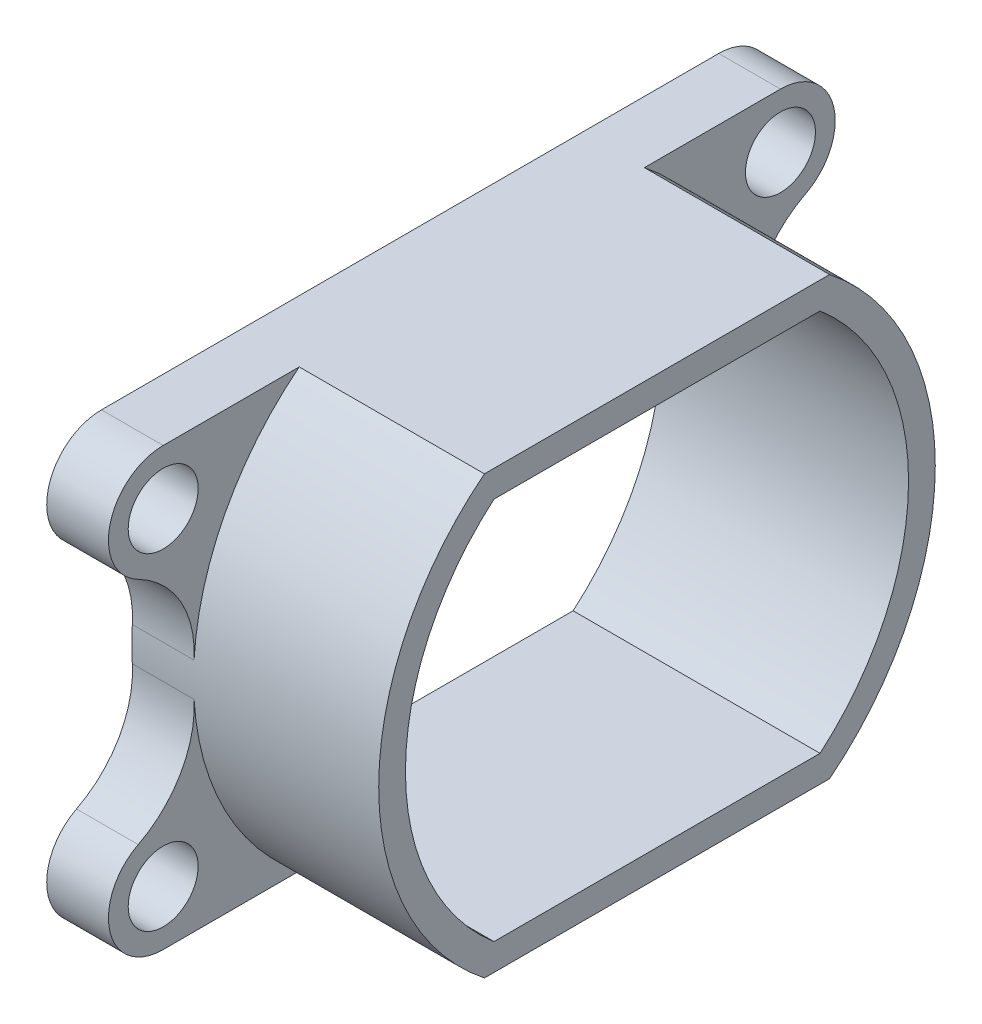
SolidWorks part; units mm, degrees
ref_plane "Front Plane" through (0, 0, 0) normal (0, 0, 1) x (1, 0, 0)
ref_plane "Top Plane" through (0, 0, 0) normal (0, 1, 0) x (1, 0, 0)
ref_plane "Right Plane" through (0, 0, 0) normal (1, 0, 0) x (0, 0, -1)
sketch "Sketch1" plane through (0, 0, 0) normal (1, 0, 0) x (0, 0, -1)
  line L0 (-7.8677, -9.16) -> (7.8677, -9.16) construction
  line L1 (-7.8677, 9.16) -> (7.8677, 9.16) construction
  line L2 (-7.8677, -9.16) -> (7.8677, 9.16) construction
  line L3 (-7.8677, 9.16) -> (7.8677, -9.16) construction
  line L4 (-7.923, 9.31) -> (7.923, 9.31)
  line L5 (-7.923, -9.31) -> (7.923, -9.31)
  line L6 (-8.3877, 10.61) -> (8.3877, 10.61)
  line L7 (-8.3877, -10.61) -> (8.3877, -10.61)
  arc A0 (-7.8677, 9.16) -> (-7.8677, -9.16) centre (0, 0) ccw construction
  arc A1 (7.8677, -9.16) -> (7.8677, 9.16) centre (0, 0) ccw construction
  arc A2 (7.923, -9.31) -> (7.923, 9.31) centre (0, 0) ccw
  arc A3 (-7.923, 9.31) -> (-7.923, -9.31) centre (0, 0) ccw
  arc A4 (8.3877, -10.61) -> (8.3877, 10.61) centre (0, 0) ccw
  arc A5 (-8.3877, 10.61) -> (-8.3877, -10.61) centre (0, 0) ccw
  point P0 (0, 0)
  point P6 (0, 0)
  point P20 (8.6275, -11.31)
  dimension "D2" = 24.15
  dimension "D1" = 18.32
  dimension "D3" = 0.15
  dimension "D4" = 1.3
extrude "Motor Holder" add sketch "Sketch1" along normal blind 12
sketch "Sketch2" plane through (0, 0, 0) normal (-1, 0, 0) x (0, 0, 1)
  line L4 (0, 0) -> (0, 27.8421) construction
  line L5 (0, 0) -> (-9.5877, 0) construction
  line L7 (8.3877, 10.61) -> (15, 10.61)
  line L24 (15.862, 5.4335) -> (12.7951, 4.383)
  line L25 (15.862, -5.4335) -> (12.7951, -4.383)
  line L26 (8.3877, -10.61) -> (15, -10.61)
  line L27 (-8.3877, -10.61) -> (-15, -10.61)
  line L28 (-15.862, -5.4335) -> (-12.7951, -4.383)
  line L29 (-15.862, 5.4335) -> (-12.7951, 4.383)
  line L30 (-8.3877, 10.61) -> (-15, 10.61)
  circle A10 centre (15, 7.95) radius 1.7
  circle A12 centre (-15, 7.95) radius 1.7
  circle A13 centre (15, -7.95) radius 1.7
  circle A14 centre (-15, -7.95) radius 1.7
  arc A16 (-8.3877, 10.61) -> (-8.3877, -10.61) centre (0, 0) ccw construction
  arc A20 (15, 10.61) -> (15.862, 5.4335) centre (15, 7.95) cw
  arc A21 (8.3877, 10.61) -> (12.7951, 4.383) centre (0, 0) cw
  arc A22 (-8.3877, 10.61) -> (-8.3877, -10.61) centre (0, 0) ccw
  arc A31 (-8.3877, 10.61) -> (-8.3877, -10.61) centre (0, 0) ccw
  arc A32 (8.3877, -10.61) -> (8.3877, 10.61) centre (0, 0) ccw construction
  arc A33 (15, -10.61) -> (15.862, -5.4335) centre (15, -7.95) ccw
  arc A34 (8.3877, -10.61) -> (12.7951, -4.383) centre (0, 0) ccw
  arc A35 (-8.3877, -10.61) -> (-12.7951, -4.383) centre (0, 0) cw
  arc A36 (-15, -10.61) -> (-15.862, -5.4335) centre (-15, -7.95) cw
  arc A37 (-15, 10.61) -> (-15.862, 5.4335) centre (-15, 7.95) ccw
  arc A38 (-8.3877, 10.61) -> (-12.7951, 4.383) centre (0, 0) ccw
  point P0 (13.8026, 3.4408)
  arc M11 (8.3877, -10.61) -> (8.3877, 10.61) centre (0, 0) ccw
  arc M13 (-8.3877, 10.61) -> (-8.3877, -10.61) centre (0, 0) ccw
  dimension "D2" = 3.4
  dimension "D1" = 7.95
  dimension "D3" = 15
extrude "Boss-Extrude1" add sketch "Sketch2" against normal blind 3 contours L30 A37 L29 A12 M13 | A36 L27 L28 A14 M13 | L26 A33 L25 A13 M11 | A20 L7 L24 A10 M11 region at (0, -5.0139, 14.2924) region at (0, 10.4983, 11.6939) region at (0, 5.0139, -14.2924) region at (0, -10.4983, -11.6939)
fillet "Fillet1" radius 5 4 edges at (1.5, -4.383, -12.7951) (1.5, 4.383, -12.7951) (1.5, -4.383, 12.7951) (1.5, 4.383, 12.7951)
